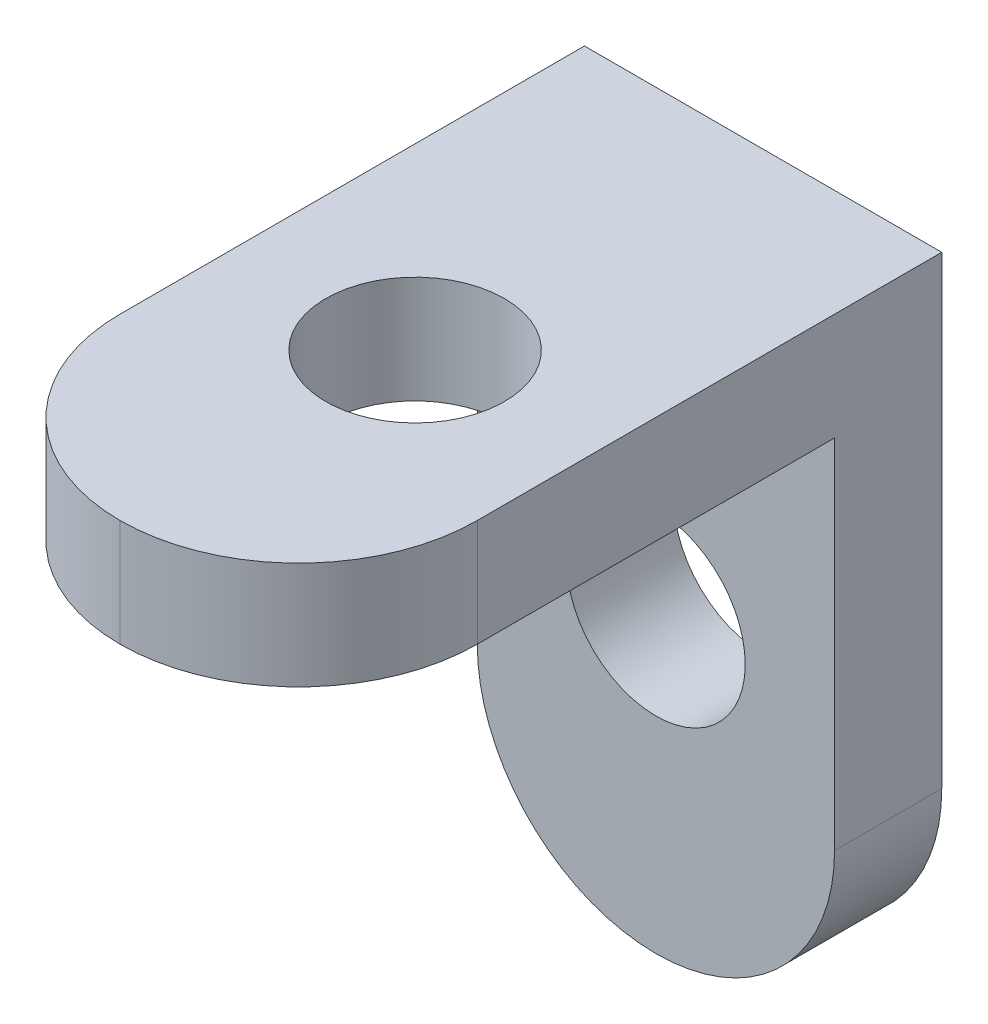
SolidWorks part; units mm, degrees
ref_plane "前视基准面" through (0, 0, 0) normal (0, 0, 1) x (1, 0, 0)
ref_plane "上视基准面" through (0, 0, 0) normal (0, 1, 0) x (1, 0, 0)
ref_plane "右视基准面" through (0, 0, 0) normal (1, 0, 0) x (0, 0, -1)
sketch "草图2" plane through (0, 0, 0) normal (0, 0, 1) x (1, 0, 0)
  line L0 (0, 0) -> (10, 0)
  line L1 (10, 0) -> (10, -18)
  line L2 (10, -18) -> (0, -18)
  line L3 (0, -18) -> (0, 0)
extrude "凸台-拉伸1" add sketch "草图2" along normal blind 3
sketch "草图3" plane through (0, 0, 3) normal (0, 0, 1) x (1, 0, 0)
  line L0 (5, 0) -> (5, -9.74) construction
  line L1 (10, 0) -> (0, 0) construction
  circle A0 centre (5, -9.74) radius 2.5
  point P6 (5, -6.8891)
extrude "切除-拉伸1" cut sketch "草图3" against normal through all
fillet "圆角1" radius 5 2 edges at (10, -18, 1.5) (0, -18, 1.5)
sketch "草图4" plane through (0, 0, 3) normal (0, 0, 1) x (1, 0, 0)
  line L0 (0, 0) -> (0, -3)
  line L1 (0, 0) -> (0, -13) construction
  line L2 (0, -3) -> (10, -3)
  line L3 (10, -13) -> (10, 0) construction
  line L4 (10, -3) -> (10, 0)
  line L5 (10, 0) -> (0, 0)
extrude "凸台-拉伸2" add sketch "草图4" along normal blind 15
fillet "圆角2" radius 5 2 edges at (10, -1.5, 18) (0, -1.5, 18)
sketch "草图5" plane through (0, -3, 0) normal (0, -1, 0) x (1, 0, 0)
  circle A0 centre (5, 11.11) radius 2.5
extrude "切除-拉伸2" cut sketch "草图5" against normal through all
sketch "草图6" plane through (0, -3, 0) normal (0, -1, 0) x (1, 0, 0)
  circle A0 centre (5, 11.11) radius 2.5
extrude "凸台-拉伸3" add sketch "草图6" against normal blind 3
sketch "草图7" plane through (0, -3, 0) normal (0, -1, 0) x (-1, 0, 0)
  circle A0 centre (-5, -12.02) radius 2.5
extrude "切除-拉伸3" cut sketch "草图7" against normal through all
sketch "草图8" plane through (0, -3, 0) normal (0, -1, 0) x (1, 0, 0)
  circle A0 centre (5, 12.02) radius 2.5809
extrude "凸台-拉伸4" add sketch "草图8" against normal blind 3
sketch "草图9" plane through (0, -3, 0) normal (0, -1, 0) x (1, 0, 0)
  line L0 (5, 3) -> (5, 8.11) construction
  line L2 (0, 3) -> (10, 3) construction
  circle A0 centre (5, 8.11) radius 2.5
extrude "切除-拉伸4" cut sketch "草图9" against normal through all
sketch "草图10" plane through (0, -3, 0) normal (0, -1, 0) x (1, 0, 0)
  circle A0 centre (5, 8.11) radius 2.5
extrude "凸台-拉伸5" add sketch "草图10" against normal blind 3
sketch "草图11" plane through (0, -3, 0) normal (0, -1, 0) x (1, 0, 0)
  line L0 (5, 3) -> (5, 7.24) construction
  line L1 (0, 3) -> (10, 3) construction
  circle A1 centre (5, 9.74) radius 2.5
extrude "切除-拉伸5" cut sketch "草图11" against normal through all
